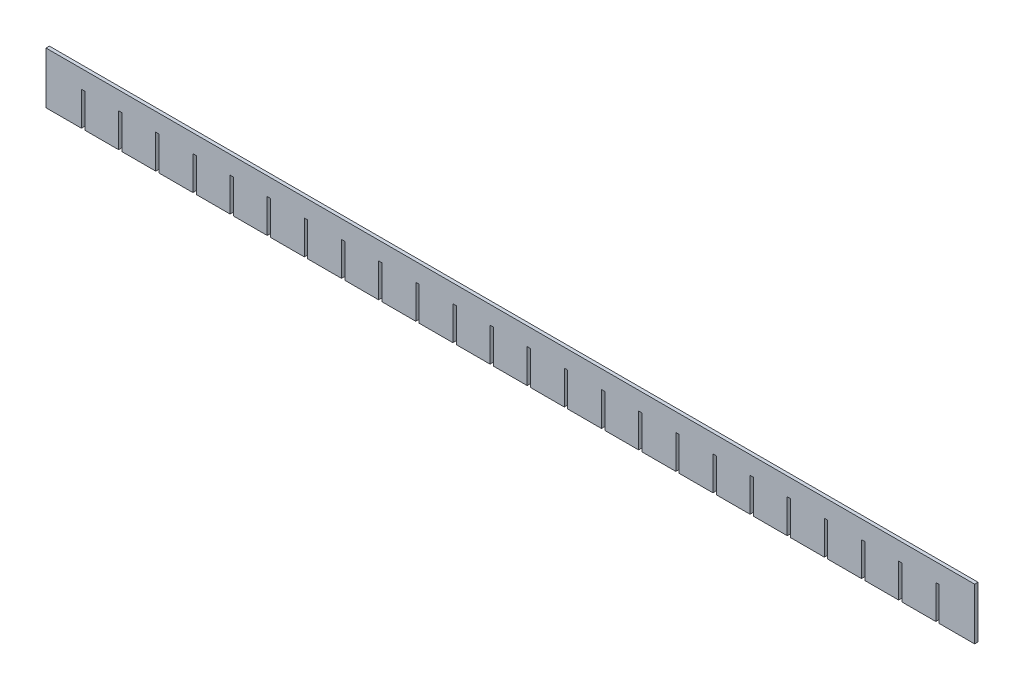
SolidWorks part; units mm, degrees
ref_plane "Ebene vorne" through (0, 0, 0) normal (0, 0, 1) x (1, 0, 0)
ref_plane "Ebene oben" through (0, 0, 0) normal (0, 1, 0) x (1, 0, 0)
ref_plane "Ebene rechts" through (0, 0, 0) normal (1, 0, 0) x (0, 0, -1)
sketch "Sketch1" plane through (0, 0, 0) normal (0, 0, 1) x (1, 0, 0)
  line L1 (-412.5, -23) -> (412.5, -23)
  line L2 (-412.5, -23) -> (-412.5, 23)
  line L3 (-412.5, 23) -> (412.5, 23)
  line L4 (412.5, -23) -> (412.5, 23)
  line L5 (-412.5, -23) -> (412.5, 23) construction
  line L6 (-412.5, 23) -> (412.5, -23) construction
  point P0 (0, 0)
  dimension "D1" = 46
  dimension "D2" = 825
extrude "Boss-Extrude1" add sketch "Sketch1" along normal blind 3
sketch "Sketch2" plane through (0, 0, 3) normal (0, 0, 1) x (1, 0, 0)
  line L6 (-412.5, -23) -> (-381, -23)
  line L7 (-412.5, -23) -> (412.5, -23) construction
  line L8 (-381, -23) -> (-381, 7)
  line L9 (-381, 7) -> (-378, 7)
  line L10 (-378, 7) -> (-378, -23)
  line L11 (-381, -23) -> (-378, -23)
  point P4 (-379.5, -23)
  dimension "D1" = 33
  dimension "D2" = 30
  dimension "D3" = 3
extrude "Cut-Extrude1" cut sketch "Sketch2" against normal through all contours L11 L10 L9 L8
pattern_linear "LPattern1" count 24 spacing 33 along (1, 0, 0) of "Cut-Extrude1"
